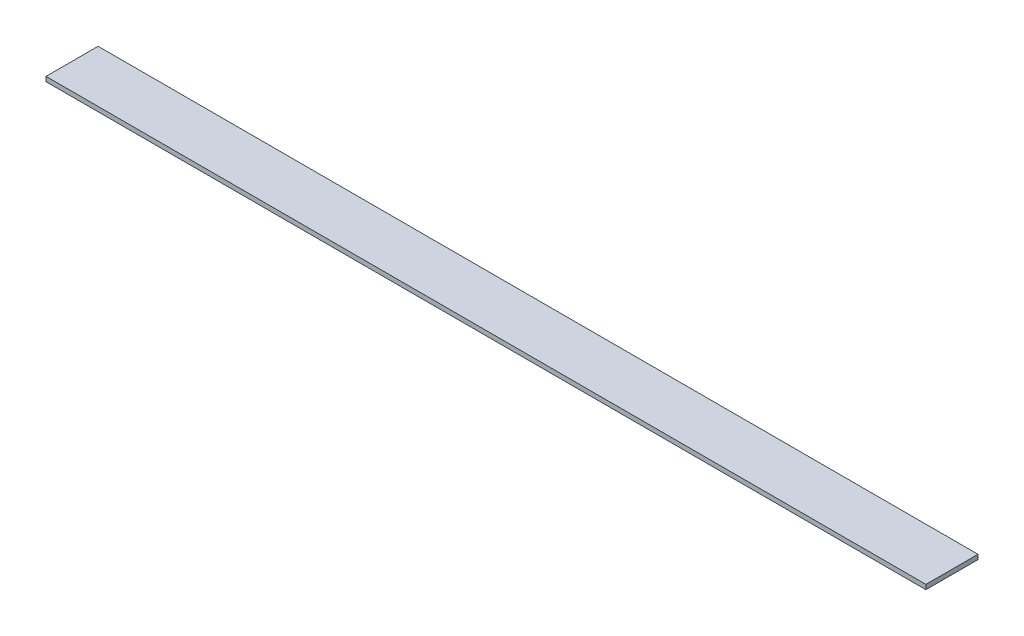
SolidWorks part; units mm, degrees
material "CK45"
ref_plane "Front Plane" through (0, 0, 0) normal (0, 0, 1) x (1, 0, 0)
ref_plane "Top Plane" through (0, 0, 0) normal (0, 1, 0) x (1, 0, 0)
ref_plane "Right Plane" through (0, 0, 0) normal (1, 0, 0) x (0, 0, -1)
sketch "Sketch1" plane through (0, 0, 0) normal (0, 1, 0) x (1, 0, 0)
  line L1 (-1140, -67.5) -> (1140, -67.5)
  line L2 (-1140, -67.5) -> (-1140, 67.5)
  line L3 (-1140, 67.5) -> (1140, 67.5)
  line L4 (1140, -67.5) -> (1140, 67.5)
  line L5 (-1140, -67.5) -> (1140, 67.5) construction
  line L6 (-1140, 67.5) -> (1140, -67.5) construction
  point P0 (0, 0)
  dimension "D1" = 2280
  dimension "1" = 135
base flange "Base-Flange1" sketch "Sketch1" thickness 12 reverse thickness direction no parameters "D1"=15
sketch "Bend-Lines1" [suppressed] plane through (0, 0, 0) normal (0, 1, 0) x (1, 0, 0)
sketch "Bounding-Box1" [suppressed] plane through (0, 0, 0) normal (0, 1, 0) x (1, 0, 0)
sheet metal parameters "Sheet-Metal2" thickness 12 parameters "D1"=3
flat pattern "Flat-Pattern2" [suppressed]
sketch "Bend-Lines2" plane through (0, 0, 0) normal (0, 1, 0) x (1, 0, 0)
sketch3d "Bounding-Box2" [suppressed]
  line L0 (1140, 67.5, 0) -> (-1140, 67.5, 0) construction
  line L1 (1140, -67.5, 0) -> (-1140, -67.5, 0) construction
  line L2 (1140, 67.5, 0) -> (1140, -67.5, 0) construction
  line L3 (-1140, 67.5, 0) -> (-1140, -67.5, 0) construction
